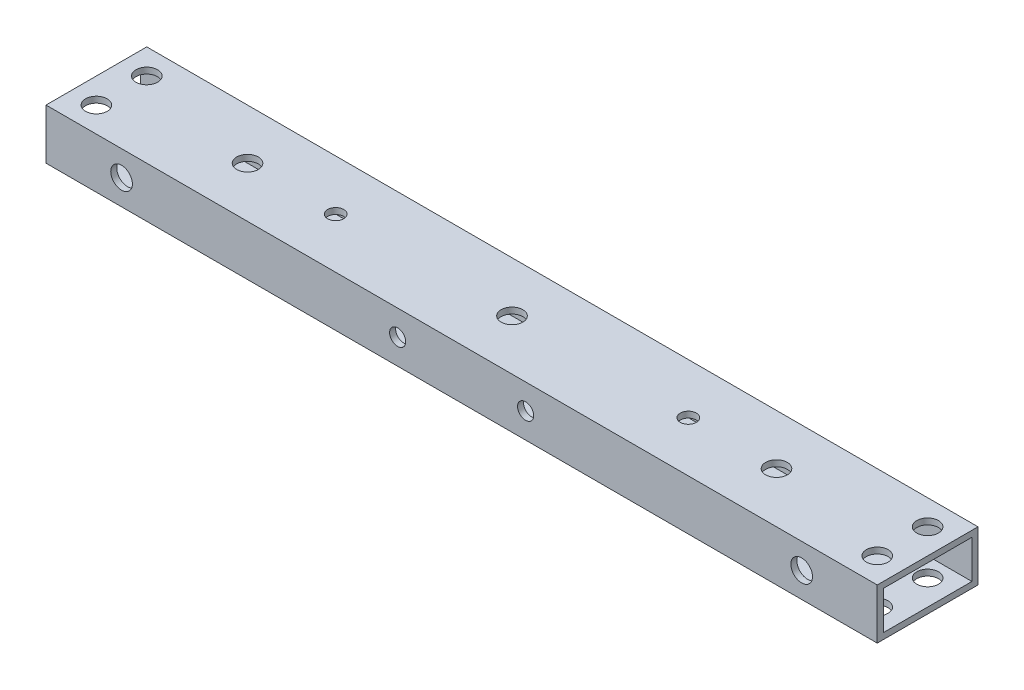
SolidWorks part; units mm, degrees
material "5052-H34"
ref_plane "正面" through (0, 0, 0) normal (0, 0, 1) x (1, 0, 0)
ref_plane "平面" through (0, 0, 0) normal (0, 1, 0) x (1, 0, 0)
ref_plane "右側面" through (0, 0, 0) normal (1, 0, 0) x (0, 0, -1)
sketch "ｽｹｯﾁ1" plane through (0, 0, 0) normal (1, 0, 0) x (0, 0, -1)
  line L1 (-10, 5) -> (10, 5)
  line L2 (-10, 5) -> (-10, -5)
  line L3 (-10, -5) -> (10, -5)
  line L4 (10, 5) -> (10, -5)
  line L5 (-10, 5) -> (10, -5) construction
  line L6 (-10, -5) -> (10, 5) construction
  point P0 (0, 0)
  dimension "D1" = 20
  dimension "D2" = 10
extrude "押し出し-薄板1" add sketch "ｽｹｯﾁ1" along normal blind 165 thin thin type one direction reverse wall 1.2
sketch "ｽｹｯﾁ2" plane through (0, 5, 0) normal (0, 1, 0) x (1, 0, 0)
  line L0 (82.5, 10) -> (82.5, -10) construction
  line L1 (165, 10) -> (0, 10) construction
  line L2 (165, -10) -> (0, -10) construction
  line L3 (82.5, 0) -> (135, 0) construction
  line L4 (160, 5) -> (160, -5) construction
  line L5 (165, 10) -> (165, -10) construction
  circle A1 centre (135, 0) radius 2.15
  circle A2 centre (30, 0) radius 2.15
  circle A4 centre (160, 5) radius 2.15
  circle A5 centre (160, -5) radius 2.15
  circle A6 centre (5, -5) radius 2.15
  circle A7 centre (5, 5) radius 2.15
  circle A8 centre (82.5, 0) radius 2.15
  circle A9 centre (117.5, 0) radius 1.6
  circle A10 centre (47.5, 0) radius 1.6
  dimension "D1" = 4.3
  dimension "D6" = 4.3
  dimension "D3" = 47.5
  dimension "D7" = 3.2
  dimension "D2" = 105
  dimension "D4" = 10
  dimension "D5" = 5
extrude "ｶｯﾄ - 押し出し1" cut sketch "ｽｹｯﾁ2" against normal through all
sketch "ｽｹｯﾁ3" plane through (0, 0, 10) normal (0, 0, 1) x (1, 0, 0)
  line L0 (82.5, 5) -> (82.5, -5) construction
  line L1 (165, 5) -> (0, 5) construction
  line L2 (165, -5) -> (0, -5) construction
  line L3 (165, 0) -> (150, 0) construction
  line L4 (165, 5) -> (165, -5) construction
  circle A0 centre (150, 0) radius 2.15
  circle A1 centre (15, 0) radius 2.15
  dimension "D1" = 4.3
  dimension "D2" = 15
extrude "ｶｯﾄ - 押し出し2" cut sketch "ｽｹｯﾁ3" against normal through all
sketch "ｽｹｯﾁ4" plane through (0, 0, 10) normal (0, 0, 1) x (1, 0, 0)
  line L0 (82.5, 5) -> (82.5, -5) construction
  line L1 (165, 5) -> (0, 5) construction
  line L2 (165, -5) -> (0, -5) construction
  line L3 (82.5, 0) -> (95.2, 0) construction
  circle A0 centre (95.2, 0) radius 1.6
  circle A1 centre (69.8, 0) radius 1.6
  dimension "D1" = 3.2
  dimension "D2" = 25.4
extrude "ｶｯﾄ - 押し出し3" cut sketch "ｽｹｯﾁ4" against normal through all
